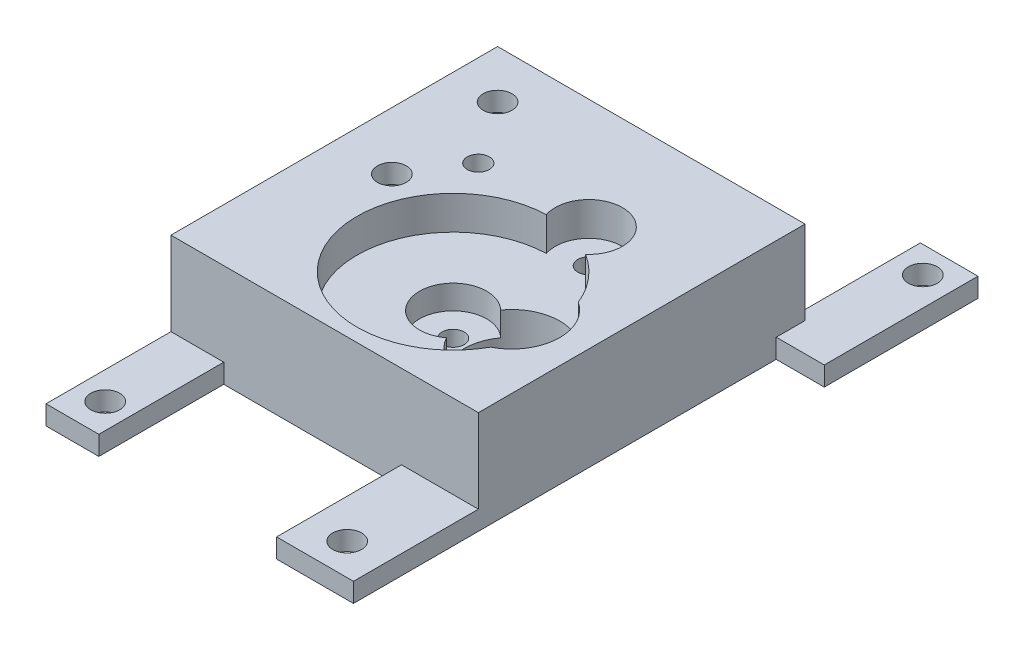
SolidWorks part; units mm, degrees
note: The reader was unsure of these and kept them because the rebuilt part matched: shared geometry of "草图1<30>", "草图1<31>", "草图1<32>", "草图2<3>", "草图1<33>", "草图1<34>", "草图1<37>".
ref_plane "前视基准面" through (0, 0, 0) normal (0, 0, 1) x (1, 0, 0)
ref_plane "上视基准面" through (0, 0, 0) normal (0, 1, 0) x (1, 0, 0)
ref_plane "右视基准面" through (0, 0, 0) normal (1, 0, 0) x (0, 0, -1)
other "Configuration Table"
sketch "草图1" plane through (0, 0, 0) normal (0, 1, 0) x (1, 0, 0)
  line L5 (-13, 23) -> (19, 23)
  line L6 (-13, 23) -> (-13, -11)
  line L7 (-13, -11) -> (19, -11)
  line L8 (19, 23) -> (19, -11)
  circle A0 centre (11.4735, 0) radius 5
  circle A1 centre (-3.4891, 11.4815) radius 1.15
  circle A2 centre (8.0109, 11.4815) radius 1.15
  circle A4 centre (-3.4891, 11.4815) radius 8.5
  circle A5 centre (8.0109, 11.4815) radius 10
  circle A7 centre (4.985, 0.3868) radius 10
  circle A8 centre (4.985, 0.3868) radius 1.15
  circle A9 centre (0, 0) radius 5.5
  circle A10 centre (0, 0) radius 2.6
  circle A11 centre (-3.4891, 11.4815) radius 3.5
  circle A12 centre (8.0109, 11.4815) radius 3.5
  circle A13 centre (4.985, 0.3868) radius 3.5
  circle A14 centre (11.4735, 0) radius 3.1
  dimension "D2" = 2.3
  dimension "D3" = 2.3
  dimension "D4" = 11.5
  dimension "D5" = 2.3
  dimension "D6" = 11.5
  dimension "D7" = 5.2
  dimension "D10" = 17
  dimension "D11" = 20
  dimension "D12" = 14
  dimension "D13" = 20
  dimension "D15" = 7
  dimension "D8" = 11
  dimension "D17" = 7
  dimension "D18" = 7
  dimension "D19" = 10
  dimension "D20" = 6.2
  dimension "D9" = 12
  dimension "D14" = 6.5
  dimension "D16" = 5
  dimension "D21" = 23
  dimension "D22" = 19
  dimension "D23" = 13
  dimension "D24" = 11
extrude "凸台-拉伸1" add sketch "草图1" along normal blind 3.5 contours L8 L7 L6 L5 | A12 | A7 | A0
extrude "凸台-拉伸2" add sketch "草图1<30>" against normal blind 2.5 contours L5 L8 L7 L6 | A0 | A13
sketch "草图1<30>" plane through (0, 0, 0) normal (0, 1, 0) x (1, 0, 0) same geometry as "草图1"
extrude "凸台-拉伸3" add sketch "草图1<31>" against normal blind 2 from surface at -2.5 contours L7 L8 L5 L6 | A0 starting at face at (8.9779, -2.5, -0.1488)
sketch "草图1<31>" plane through (0, 0, 0) normal (0, 1, 0) x (1, 0, 0) same geometry as "草图1"
extrude "凸台-拉伸4" add sketch "草图1<32>" against normal blind 2.7 from surface at -4.5 contours L5 L8 L7 L6 | A14 starting at face at (11.4735, -4.5, 5)
sketch "草图1<32>" plane through (0, 0, 0) normal (0, 1, 0) x (1, 0, 0) same geometry as "草图1"
sketch "草图2" plane through (0, -7.2, 0) normal (0, -1, 0) x (1, 0, 0)
  circle A0 centre (-8, -18) radius 1.5
  circle A1 centre (-7, -6) radius 1.5
  circle A2 centre (-8, -18) radius 2.25
  circle A3 centre (-7, -6) radius 2.25
  dimension "D1" = 3
  dimension "D2" = 4.5
extrude "切除-拉伸1" cut sketch "草图2" against normal through all contours A0 | A1
extrude "切除-拉伸2" cut sketch "草图2<3>" against normal offset from surface (8.7 mm away) 2 contours A2 | A3 up to face at (-8, 3.5, -19.5)
sketch "草图2<3>" plane through (0, -7.2, 0) normal (0, -1, 0) x (1, 0, 0) same geometry as "草图2"
extrude "切除-拉伸3" cut sketch "草图1<33>" against normal blind 4 contours A1 | A2
sketch "草图1<33>" plane through (0, 0, 0) normal (0, 1, 0) x (1, 0, 0) same geometry as "草图1"
sketch "草图3" plane through (0, -7.2, 0) normal (0, -1, 0) x (1, 0, 0)
  line L0 (19, 11) -> (-13, 11) construction
  line L1 (-13, 11) -> (-7.5, 11)
  line L2 (-13, 11) -> (-13, 24)
  line L3 (-13, 24) -> (-7.5, 24)
  line L4 (-7.5, 11) -> (-7.5, 24)
  line L5 (11, 11) -> (19, 11)
  line L6 (11, 11) -> (11, 24)
  line L7 (11, 24) -> (19, 24)
  line L8 (19, 11) -> (19, 24)
  line L9 (19, -23) -> (-13, -23) construction
  line L10 (18, -23) -> (24, -23)
  line L11 (18, -23) -> (18, -36)
  line L12 (18, -36) -> (24, -36)
  line L13 (24, -23) -> (24, -36)
  line L14 (19, 11) -> (19, -23) construction
  line L15 (19, -23) -> (24, -23)
  line L16 (19, -23) -> (19, -20)
  line L17 (19, -20) -> (24, -20)
  line L18 (24, -23) -> (24, -20)
  circle A0 centre (15.0583, 20.7147) radius 1.5
  circle A1 centre (-10.1215, 20.7147) radius 1.5
  circle A2 centre (21.0212, -33.234) radius 1.5
  dimension "D8" = 3
  dimension "D1" = 13
  dimension "D2" = 5.5
  dimension "D3" = 8
  dimension "D4" = 3
  dimension "D5" = 6
  dimension "D6" = 1
  dimension "D7" = 13
extrude "凸台-拉伸5" add sketch "草图3" against normal blind 2 contours L4 L3 L2 L1 | L8 L7 L6 L5 | A0 | A1 | L10 L11 L12 L13 | A2 | L15 L16 L17 L18
extrude "切除-拉伸4" cut sketch "草图1<34>" against normal offset from surface (5.2 mm away) 2 contours A8 up to face at (8.5833, -7.2, -3.3333)
sketch "草图1<34>" plane through (0, 0, 0) normal (0, 1, 0) x (1, 0, 0) same geometry as "草图1"
extrude "切除-拉伸6" cut sketch "草图1<37>" against normal blind 2 from surface at 3.5 contours A1 starting at face at (-8, 3.5, -19.5)
sketch "草图1<37>" plane through (0, 0, 0) normal (0, 1, 0) x (1, 0, 0) same geometry as "草图1"
